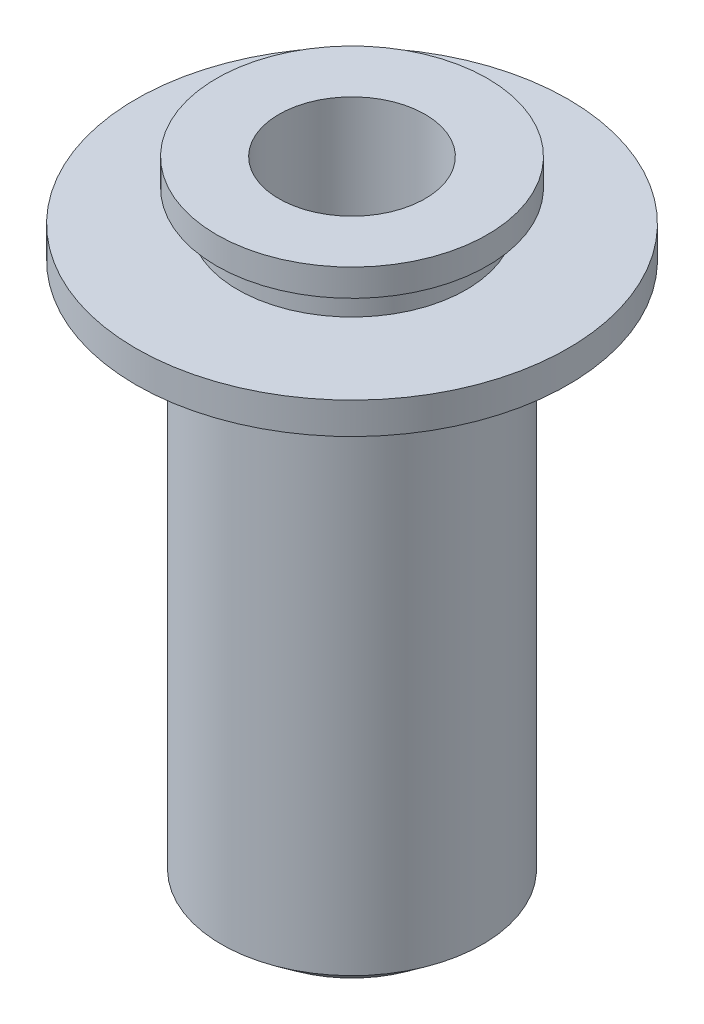
SolidWorks part; units mm, degrees
ref_plane "Спереди" through (0, 0, 0) normal (0, 0, 1) x (1, 0, 0)
ref_plane "Сверху" through (0, 0, 0) normal (0, 1, 0) x (1, 0, 0)
ref_plane "Справа" through (0, 0, 0) normal (1, 0, 0) x (0, 0, -1)
sketch "Эскиз1" plane through (0, 0, 0) normal (0, 0, 1) x (1, 0, 0)
  line L0 (7.0021, 0) -> (7.0021, 61.5922)
  line L1 (7.0021, 61.5922) -> (12.9668, 61.5922)
  line L2 (12.9668, 61.5922) -> (12.9668, 58.9989)
  line L3 (12.9668, 58.9989) -> (10.9422, 58.9989)
  line L4 (10.9422, 58.9989) -> (10.9422, 56.0159)
  line L5 (10.9422, 56.0159) -> (20.6829, 56.0159)
  line L6 (20.6829, 56.0159) -> (20.6829, 52.9943)
  line L7 (20.6829, 52.9943) -> (12.4928, 52.9943)
  line L8 (12.4928, 52.9943) -> (12.4928, 2.4961)
  line L9 (12.4928, 2.4961) -> (9.2515, 0)
  line L10 (9.2515, 0) -> (7.0021, 0)
  line L11 (0, -11.4414) -> (0, 79.8018) construction
revolve "Повернуть1" add sketch "Эскиз1" angle 360 about L11
